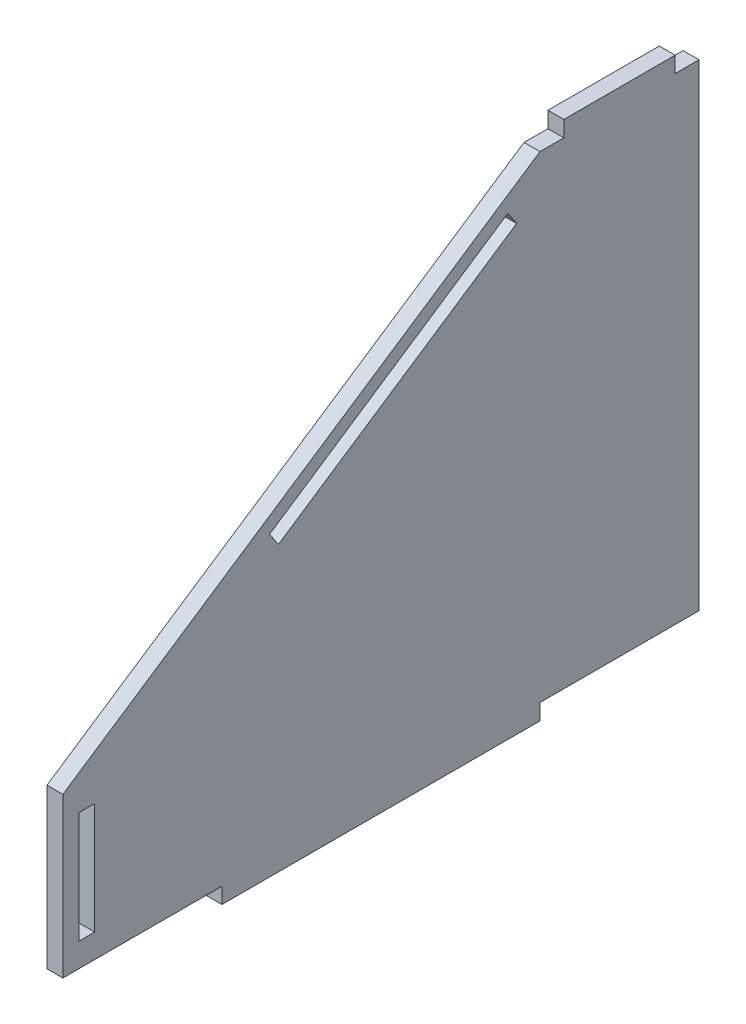
SolidWorks part; units mm, degrees
ref_plane "Alzado" through (0, 0, 0) normal (0, 0, 1) x (1, 0, 0)
ref_plane "Planta" through (0, 0, 0) normal (0, 1, 0) x (1, 0, 0)
ref_plane "Vista lateral" through (0, 0, 0) normal (1, 0, 0) x (0, 0, -1)
sketch "Croquis1" plane through (0, 0, 0) normal (1, 0, 0) x (0, 0, -1)
  line L0 (150, 150) -> (0, 50)
  line L1 (0, 0) -> (50, 0)
  line L2 (0, 0) -> (0, 50)
  line L3 (150, 150) -> (157.5, 150)
  line L4 (200, 0) -> (200, 150)
  line L6 (5, 42.5) -> (10, 42.5)
  line L7 (5, 42.5) -> (5, 7.5)
  line L8 (5, 7.5) -> (10, 7.5)
  line L9 (50, 0) -> (50, -5)
  line L10 (50, -5) -> (150, -5)
  line L11 (150, 0) -> (150, -5)
  line L12 (10, 42.5) -> (10, 7.5)
  line L13 (192.5, 150) -> (200, 150)
  line L14 (150, 0) -> (200, 0)
  line L15 (65, 88.3333) -> (139.8845, 138.2564)
  line L16 (157.5, 150) -> (157.5, 155)
  line L17 (157.5, 155) -> (192.5, 155)
  line L18 (192.5, 150) -> (192.5, 155)
  line L19 (139.8845, 138.2564) -> (142.658, 134.0961)
  line L20 (142.658, 134.0961) -> (67.7735, 84.1731)
  line L21 (67.7735, 84.1731) -> (65, 88.3333)
  line L22 (5, 53.3333) -> (5, 0) construction
  line L23 (65, 88.3333) -> (5, 48.3333) construction
  dimension "D6" = 35
  dimension "D10" = 7.5
  dimension "D1" = 150
  dimension "D2" = 200
  dimension "D3" = 50
  dimension "D4" = 50
  dimension "D5" = 7.5
  dimension "D7" = 100
  dimension "D8" = 50
  dimension "D9" = 5
  dimension "D11" = 5
  dimension "D31" = 35
  dimension "D32" = 5
  dimension "D33" = 90
  dimension "D34" = 15
  dimension "D35" = 5
  dimension "D36" = 5
  dimension "D37" = 35
extrude "Saliente-Extruir1" add sketch "Croquis1" along normal blind 5
